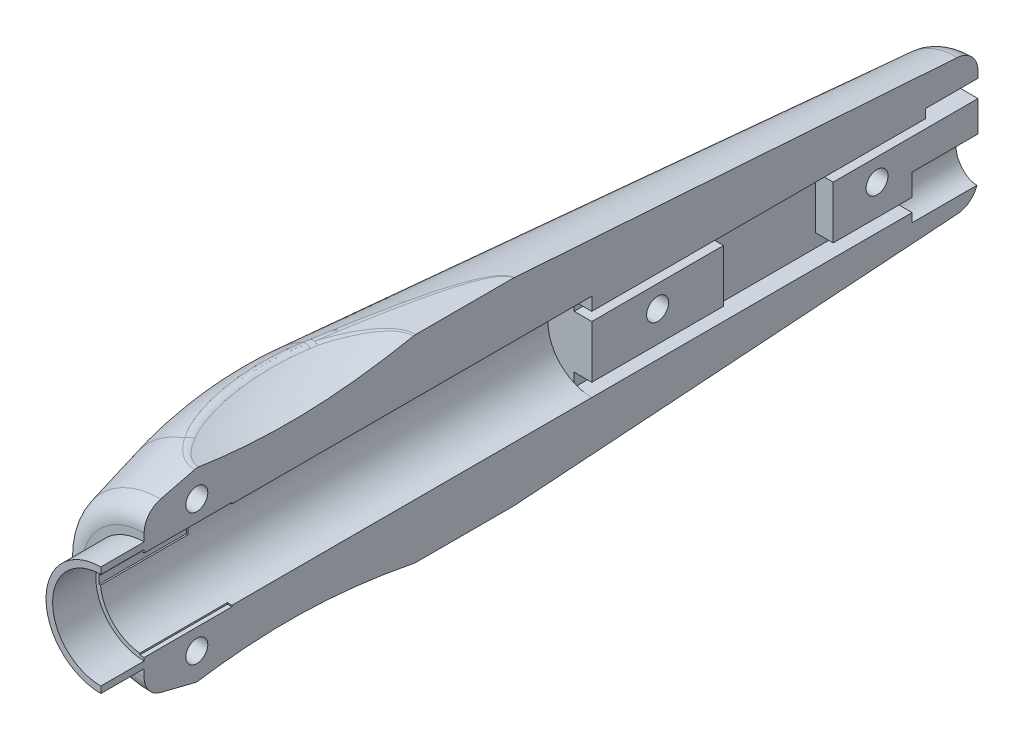
SolidWorks part; units mm, degrees
ref_plane "Ön Düzlem" through (0, 0, 0) normal (0, 0, 1) x (1, 0, 0)
ref_plane "Üst Düzlem" through (0, 0, 0) normal (0, 1, 0) x (1, 0, 0)
ref_plane "Sağ Düzlem" through (0, 0, 0) normal (1, 0, 0) x (0, 0, -1)
sketch "Sketch1" plane through (0, 0, 0) normal (0, 0, 1) x (1, 0, 0)
  circle A0 centre (0, 0) radius 5
  circle A1 centre (0, 0) radius 11.25
  dimension "D1" = 10
  dimension "D2" = 22.5
extrude "Boss-Extrude1" add sketch "Sketch1" along normal blind 51 and the other way blind 35
sketch "Sketch2" plane through (0, 0, -35) normal (0, 0, -1) x (-1, 0, 0)
  circle A0 centre (0, 0) radius 11.25
extrude "Boss-Extrude2" add sketch "Sketch2" along normal blind 9
sketch "Sketch3" plane through (0, 0, -44) normal (0, 0, -1) x (-1, 0, 0)
  line L0 (-2, 4.5) -> (-3, 3.5)
  line L1 (-3, 2.5) -> (3, 2.5)
  line L2 (-3, 2.5) -> (-3, 3.5)
  line L3 (-2, 4.5) -> (2, 4.5)
  line L4 (3, 2.5) -> (3, 3.5)
  line L5 (3, 3.5) -> (2, 4.5)
  point P4 (0, 2.5)
  dimension "D1" = 6
  dimension "D3" = 2.5
  dimension "D4" = 4
  dimension "D5" = 45
extrude "Cut-Extrude1" cut sketch "Sketch3" against normal blind 6
sketch "Sketch4" plane through (0, 0, -44) normal (0, 0, -1) x (-1, 0, 0)
  line L1 (-5, -1) -> (5, -1)
  line L2 (-5, -1) -> (-5, -3.5)
  line L3 (-5, -3.5) -> (5, -3.5)
  line L4 (5, -1) -> (5, -3.5)
  point P4 (0, -3.5)
  dimension "D1" = 10
  dimension "D2" = 2.5
  dimension "D3" = 1
extrude "Cut-Extrude2" cut sketch "Sketch4" against normal blind 5 from offset 2.5 offset against normal yes
sketch "Sketch5" plane through (0, 0, -44) normal (0, 0, -1) x (-1, 0, 0)
  circle A0 centre (0, -3.5) radius 2.5
  dimension "D1" = 5
  dimension "D2" = 3.5
extrude "Cut-Extrude3" cut sketch "Sketch5" against normal blind 7.5
sketch "Sketch6" plane through (0, 0, 51) normal (0, 0, 1) x (1, 0, 0)
  line L0 (0.5, 4.9) -> (-0.5, 4.9)
  line L1 (-4.9, 0.5) -> (-5.15, 0.5)
  line L2 (-4.9, 0.5) -> (-4.9, -0.5)
  line L3 (-4.9, -0.5) -> (-5.15, -0.5)
  line L4 (-5.15, 0.5) -> (-5.15, -0.5)
  line L5 (0.5, 4.9) -> (0.5, 5.15)
  line L6 (0.5, 5.15) -> (-0.5, 5.15)
  line L7 (-0.5, 4.9) -> (-0.5, 5.15)
  line L8 (4.9, -0.5) -> (4.9, 0.5)
  line L9 (4.9, -0.5) -> (5.15, -0.5)
  line L10 (5.15, -0.5) -> (5.15, 0.5)
  line L11 (4.9, 0.5) -> (5.15, 0.5)
  line L12 (-0.5, -4.9) -> (0.5, -4.9)
  line L13 (-0.5, -4.9) -> (-0.5, -5.15)
  line L14 (-0.5, -5.15) -> (0.5, -5.15)
  line L15 (0.5, -4.9) -> (0.5, -5.15)
  point P4 (-4.9, 0)
  point P21 (0, 0)
  dimension "D1" = 1
  dimension "D2" = 0.25
  dimension "D3" = 4.9
  dimension "D4" = 4
extrude "Cut-Extrude4" cut sketch "Sketch6" against normal blind 10
sketch "Sketch7" plane through (0, 0, 51) normal (0, 0, 1) x (1, 0, 0)
  line L0 (-11.25, 11.25) -> (11.25, -11.25) construction
  line L1 (-11.25, 11.25) -> (11.25, 11.25)
  line L2 (-11.25, 11.25) -> (-11.25, -11.25)
  line L3 (-11.25, -11.25) -> (11.25, -11.25)
  line L4 (11.25, 11.25) -> (11.25, -11.25)
  circle A0 centre (0, 0) radius 7.5
  point P4 (0, 0)
  dimension "D3" = 15
  dimension "D1" = 22.5
  dimension "D2" = 22.5
extrude "Boss-Extrude3" add sketch "Sketch7" against normal blind 55
sketch "Sketch11" plane through (0, 0, 51) normal (0, 0, 1) x (1, 0, 0)
  circle A0 centre (0, 0) radius 5.5
  circle A1 centre (0, 0) radius 6.25
  dimension "D1" = 12.5
  dimension "D2" = 11
extrude "Boss-Extrude4" add sketch "Sketch11" along normal blind 5
sketch "Sketch14" plane through (11.25, 0, 0) normal (1, 0, 0) x (0, 0, -1)
  line L1 (-70.4093, 18.7396) -> (-55.9318, 18.7396)
  line L2 (-70.4093, 18.7396) -> (-70.4093, -13.801)
  line L3 (-70.4093, -13.801) -> (-55.9318, -13.801)
  line L4 (-55.9318, 18.7396) -> (-55.9318, -13.801)
extrude "Cut-Extrude5" cut sketch "Sketch14" against normal blind 30
sketch "Sketch15" plane through (0, 0, 0) normal (0, 1, 0) x (1, 0, 0)
  line L0 (-7.5, 44.75) -> (-13.0767, -35)
  line L1 (-13.0767, -35) -> (-6.8248, -60)
  line L2 (11.25, 44) -> (-11.25, 44) construction
  line L3 (-7.5, 44.75) -> (-52.5, 44.75)
  line L4 (-52.5, 44.75) -> (-52.5, -598.78)
  line L5 (0, 0) -> (0, 16.5551) construction
  line L6 (-6.8248, -60) -> (-14.8248, -60)
  line L7 (-14.8248, -60) -> (-52.5, -598.78)
  dimension "D1" = 7.5
  dimension "D2" = 0.75
  dimension "D3" = 45
  dimension "D4" = 86
  dimension "D5" = 8
  dimension "D6" = 35
  dimension "D7" = 60
revolve "Cut-Revolve2" cut sketch "Sketch15" angle 360 about L5
ref_plane "Plane2" through (0, 22.25, 0) normal (0, 1, 0) x (1, 0, 0)
sketch "Sketch17" plane through (0, 22.25, 0) normal (0, 1, 0) x (1, 0, 0)
  line L0 (0, 0) -> (0, -1000) construction
  line L1 (0, 10) -> (-7.5, -7.5) construction
  line L2 (-7.5, -7.5) -> (7.5, -7.5) construction
  line L3 (7.5, -7.5) -> (-12.5, -34.5) construction
  line L4 (-12.5, -34.5) -> (12.5, -34.5) construction
  line L5 (12.5, -34.5) -> (-7.5, -61.5) construction
  line L6 (-7.5, -61.5) -> (7.5, -61.5) construction
  line L7 (7.5, -61.5) -> (0, -79) construction
  line L8 (0, 10) -> (0, -79)
  spline S0 degree 3 poles (0, 10) (-6.8374, -3.5833) (-18.1626, -34.5) (-6.8374, -65.4167) (0, -79) knots 0 0 0 0 0.5 1 1 1 1
  point P5 (0, -7.5)
  point P12 (0, -34.5)
  point P13 (0, -61.5)
  dimension "D1" = 1000
  dimension "D2" = 17.5
  dimension "D3" = 17.5
  dimension "D4" = 27
  dimension "D5" = 27
  dimension "D6" = 15
  dimension "D7" = 25
  dimension "D8" = 15
  dimension "D9" = 10
revolve "Cut-Revolve3" cut sketch "Sketch17" angle 360 about L8
pattern_circular "CirPattern1" count 4 over 360 about axis through (0, 0, 56) along (0, 0, -1) of "Cut-Revolve3"
fillet "Fillet3" radius 1.25 4 edges at (-0.0704, -11.25, 20.1749) (11.25, -0.0704, 20.1749) (0.0704, 11.25, 20.1749) (-11.25, 0.0704, 20.1749)
fillet "Fillet6" radius 2.5 1 edges at (-7.5524, 0, -44)
fillet "Fillet7" radius 50 4 edges at (-9.2466, -9.2466, 35) (9.2466, -9.2466, 35) (9.2466, 9.2466, 35) (-9.2466, 9.2466, 35)
fillet "Fillet8" radius 2.5 1 edges at (9.0755, 0, 51)
fillet "Fillet9" radius 1.25 30 edges at (-4.9888, -10.9245, 38.5139) (-0.3761, -10.5748, 44.9779) (4.4042, -10.8271, 40.3019) (5.8141, -11.2204, 31.4351) (10.9245, -4.9888, 38.5139) (10.5748, -0.3761, 44.9779) (10.8271, 4.4042, 40.3019) (11.2204, 5.8141, 31.4351) (5.8104, 11.2032, 32.1337) (4.9888, 10.9245, 38.5139) (0.3761, 10.5748, 44.9779) (-4.4042, 10.8271, 40.3019) (-5.8141, 11.2204, 31.4351) (-11.2032, 5.8104, 32.1337) (-10.9245, 4.9888, 38.5139) (-10.5748, 0.3761, 44.9779) (-10.8271, -4.4042, 40.3019) (-11.2204, -5.8141, 31.4351) (-0.3483, -11.25, 8.9546) (11.25, -0.3483, 8.9546) (0.3483, 11.25, 8.9546) (-11.25, 0.3483, 8.9546)
sketch "Sketch18" plane through (0, 0, -35) normal (0, 0, 1) x (1, 0, 0)
  circle A0 centre (0, 0) radius 5
extrude "Boss-Extrude5" add sketch "Sketch18" along normal blind 35
sketch "Sketch19" plane through (0, 0, 0) normal (0, 0, 1) x (1, 0, 0)
  line L1 (22.7514, 22.4739) -> (0, 22.4739)
  line L2 (22.7514, 22.4739) -> (22.7514, -25.734)
  line L3 (22.7514, -25.734) -> (0, -25.734)
  line L4 (0, 22.4739) -> (0, -25.734)
extrude "Cut-Extrude6" cut sketch "Sketch19" against normal blind 64 and the other way blind 86
sketch "Sketch20" plane through (0, 0, 0) normal (1, 0, 0) x (0, 0, -1)
  line L0 (0, 5) -> (0, -5) construction
  line L1 (0, 3.5) -> (38, 3.5)
  line L2 (0, 3.5) -> (0, 2.5)
  line L3 (0, 2.5) -> (15, 2.5)
  line L4 (38, 3.5) -> (38, 2.5)
  line L5 (0, -5) -> (0, 5) construction
  line L6 (0, -3.5) -> (15, -3.5)
  line L7 (0, -3.5) -> (0, -5)
  line L8 (0, -5) -> (36.5, -5)
  line L9 (36.5, -3.5) -> (36.5, -5)
  line L10 (36.5, -6) -> (36.5, -3.5) construction
  line L12 (15, 2.5) -> (15, -3.5)
  line L14 (27.5, 2.5) -> (27.5, -3.5)
  line L15 (0, -5) -> (-41, -5) construction
  line L16 (38, 3.5) -> (44, 3.5) construction
  line L17 (38, 2.5) -> (38, 4.5) construction
  line L18 (38, 2.5) -> (44, 2.5) construction
  line L20 (36.5, -3.5) -> (41.5, -3.5) construction
  line L21 (36.5, -1) -> (36.5, -6) construction
  line L22 (27.5, 2.5) -> (38, 2.5)
  line L23 (27.5, -3.5) -> (36.5, -3.5)
  dimension "D1" = 9
  dimension "D2" = 15
extrude "Cut-Extrude8" cut sketch "Sketch20" against normal blind 2
sketch "Sketch21" plane through (0, 0, 0) normal (1, 0, 0) x (0, 0, -1)
  circle A0 centre (7.5, 0) radius 1.25
  circle A1 centre (32.5, 0) radius 1.25
  circle A2 centre (-45, 7.5) radius 1.25
  circle A3 centre (-45, -7.5) radius 1.25
  dimension "D1" = 2.5
  dimension "D3" = 2.5
  dimension "D7" = 2.5
  dimension "D8" = 2.5
  dimension "D2" = 7.5
  dimension "D4" = 25
  dimension "D5" = 45
  dimension "D6" = 45
  dimension "D9" = 7.5
  dimension "D10" = 7.5
extrude "Cut-Extrude9" cut sketch "Sketch21" against normal blind 3
